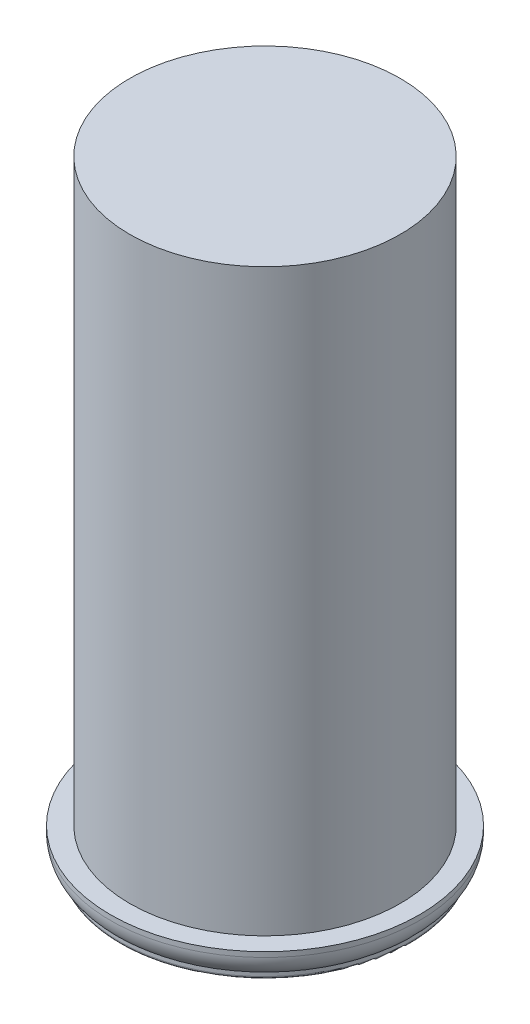
SolidWorks part; units mm, degrees
ref_plane "Front Plane" through (0, 0, 0) normal (0, 0, 1) x (1, 0, 0)
ref_plane "Top Plane" through (0, 0, 0) normal (0, 1, 0) x (1, 0, 0)
ref_plane "Right Plane" through (0, 0, 0) normal (1, 0, 0) x (0, 0, -1)
sketch "Sketch1" plane through (0, 0, 0) normal (0, 1, 0) x (1, 0, 0)
  circle A0 centre (0, 0) radius 16
  dimension "D1" = 32
extrude "Boss-Extrude1" add sketch "Sketch1" along normal blind 2.54
sketch "Sketch2" plane through (0, 2.54, 0) normal (0, 1, 0) x (1, 0, 0)
  circle A0 centre (0, 0) radius 14
  dimension "D1" = 28
extrude "Boss-Extrude2" add sketch "Sketch2" along normal blind 60
sketch "Sketch3" plane through (0, 0, 0) normal (0, -1, 0) x (1, 0, 0)
  circle A0 centre (0, 0) radius 15
  dimension "D1" = 30
extrude "Boss-Extrude3" add sketch "Sketch3" along normal blind 2.54
dome "Dome1" faces to dome 1 distance 12.7 reverse direction yes elliptical dome no face at (0, -2.54, -15) parameters "D1"=12.7
fillet "Fillet1" radius 2.54 1 edges at (0, 0, 16)
fillet "Fillet2" radius 0.254 1 edges at (0, -2.54, -15)
